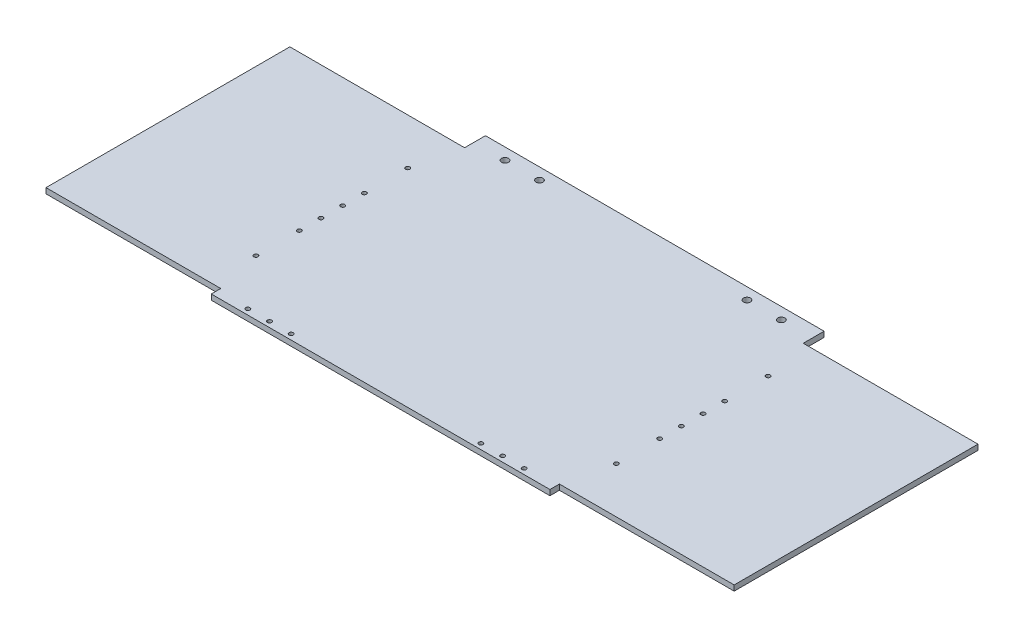
SolidWorks part; units mm, degrees
ref_plane "Front Plane" through (0, 0, 0) normal (0, 0, 1) x (1, 0, 0)
ref_plane "Top Plane" through (0, 0, 0) normal (0, 1, 0) x (1, 0, 0)
ref_plane "Right Plane" through (0, 0, 0) normal (1, 0, 0) x (0, 0, -1)
sketch "Sketch1" plane through (0, 0, 0) normal (0, 1, 0) x (1, 0, 0)
  line L0 (129, 0) -> (129, -7)
  line L1 (0, 0) -> (129, 0)
  line L2 (0, 0) -> (0, 180)
  line L3 (0, 180) -> (129, 180)
  line L4 (508, 0) -> (508, 180)
  line L5 (129, -7) -> (379, -7)
  line L6 (379, -7) -> (379, 0)
  line L7 (0, 90) -> (508, 90) construction
  line L8 (129, 180) -> (129, 195.398)
  line L9 (129, 195.398) -> (379, 195.398)
  line L10 (379, 195.398) -> (379, 180)
  line L11 (254, 195.398) -> (254, -38.1) construction
  line L12 (379, 0) -> (508, 0)
  line L13 (379, 180) -> (508, 180)
  line L14 (129, 186.858) -> (379, 186.858) construction
  line L15 (129, -3) -> (254, -3) construction
  circle A0 centre (152, 186.858) radius 2.564
  circle A1 centre (177.4, 186.858) radius 2.564
  circle A4 centre (152, -3) radius 1.55
  circle A5 centre (184, -3) radius 1.55
  circle A8 centre (330.6, 186.858) radius 2.564
  circle A9 centre (356, 186.858) radius 2.564
  circle A10 centre (168, -3) radius 1.55
  circle A11 centre (324, -3) radius 1.55
  circle A12 centre (340, -3) radius 1.55
  circle A13 centre (356, -3) radius 1.55
  circle A14 centre (121, 146) radius 1.55
  circle A15 centre (121, 114) radius 1.55
  circle A16 centre (121, 98) radius 1.55
  circle A17 centre (121, 82) radius 1.55
  circle A18 centre (121, 66) radius 1.55
  circle A19 centre (121, 34) radius 1.55
  circle A20 centre (387, 146) radius 1.55
  circle A21 centre (387, 114) radius 1.55
  circle A22 centre (387, 98) radius 1.55
  circle A23 centre (387, 82) radius 1.55
  circle A24 centre (387, 66) radius 1.55
  circle A25 centre (387, 34) radius 1.55
  point P10 (254, 90)
  point P46 (133, 136.1068)
  point P67 (121.638, 146)
  dimension "D7" = 3.1
  dimension "D9" = 5.128
  dimension "D16" = 3.1
  dimension "D1" = 180
  dimension "D2" = 508
  dimension "D3" = 250
  dimension "D5" = 250
  dimension "D8" = 8.54
  dimension "D10" = 25.4
  dimension "D11" = 23
  dimension "D6" = 6.858
  dimension "D12" = 16
  dimension "D13" = 16
  dimension "D14" = 23
  dimension "D15" = 4
  dimension "D4" = 3
  dimension "D17" = 32
  dimension "D19" = 16
  dimension "D20" = 8
  dimension "D18" = 8
extrude "Boss-Extrude1" add sketch "Sketch1" along normal blind 4
equation "\"cf_tube_outer_diameter\"= 25mm"
equation "\"cf_tube_inner_diameter\" = 21mm"
equation "\"mid_plate_mid_to_top\" = 100mm"
equation "\"mid_plate_mid_to_bottom\" = 30mm"
equation "\"mid_plate_horizontal_spacing\"=250mm"
equation "\"cf_plate_thickness\" =4mm"
equation "\"mid_tube_length\" = 500mm"
equation "\"mid_plate_bottom_width\" = 180mm"
equation "\"D1@Sketch1\"=\"mid_plate_bottom_width\""
equation "\"D2@Sketch1\"=\"mid_tube_length\"+\"cf_plate_thickness\"*2"
equation "\"D1@Boss-Extrude1\"=\"cf_plate_thickness\""
equation "\"D5@Sketch1\"=\"mid_plate_horizontal_spacing\""
equation "\"D3@Sketch1\"=\"mid_plate_horizontal_spacing\""
